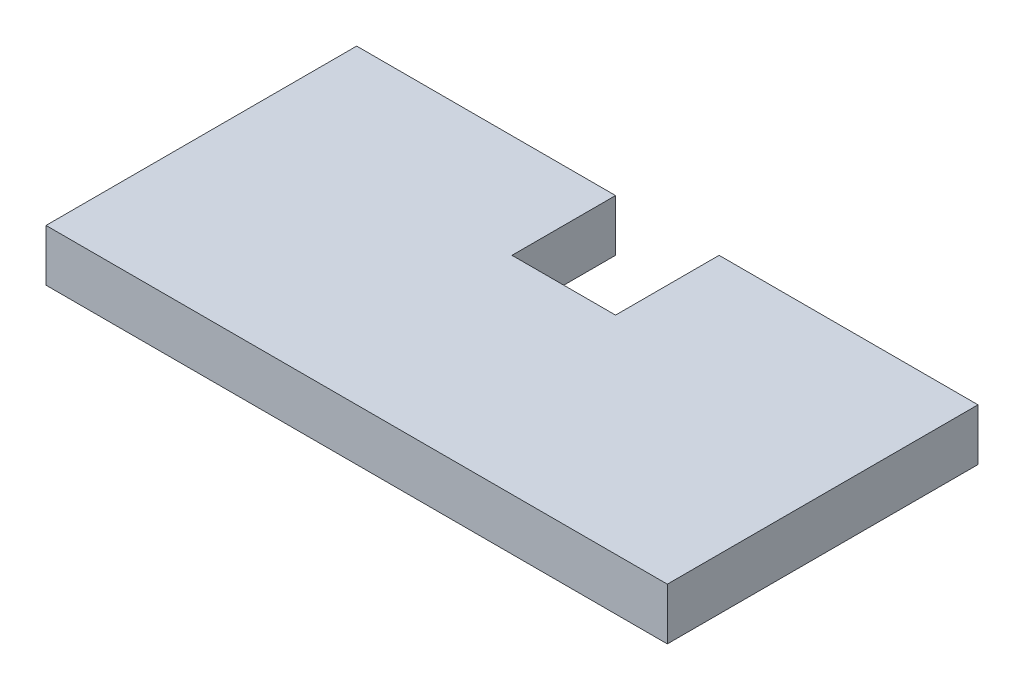
SolidWorks part; units mm, degrees
ref_plane "Front Plane" through (0, 0, 0) normal (0, 0, 1) x (1, 0, 0)
ref_plane "Top Plane" through (0, 0, 0) normal (0, 1, 0) x (1, 0, 0)
ref_plane "Right Plane" through (0, 0, 0) normal (1, 0, 0) x (0, 0, -1)
sketch "Sketch1" plane through (0, 0, 0) normal (0, 1, 0) x (1, 0, 0)
  line L1 (-516.0526, 370.5409) -> (83.9474, 370.5409)
  line L2 (-516.0526, 370.5409) -> (-516.0526, 70.5409)
  line L3 (-516.0526, 70.5409) -> (83.9474, 70.5409)
  line L4 (83.9474, 370.5409) -> (83.9474, 70.5409)
  dimension "D1" = 600
  dimension "D2" = 300
extrude "Boss-Extrude1" add sketch "Sketch1" along normal blind 50 contours L3 L4 L1 L2
sketch "Sketch2" plane through (0, 0, -370.5409) normal (0, 0, -1) x (-1, 0, 0)
  line L0 (516.0526, 50) -> (-83.9474, 50) construction
  line L1 (166.0526, 50) -> (266.0526, 50)
  line L2 (166.0526, 50) -> (166.0526, 0)
  line L3 (166.0526, 0) -> (266.0526, 0)
  line L4 (266.0526, 50) -> (266.0526, 0)
  line L5 (516.0526, 0) -> (-83.9474, 0) construction
  line L6 (-83.9474, 50) -> (-83.9474, 0) construction
  dimension "D1" = 100
  dimension "D2" = 250
  dimension "D3" = 50
extrude "Cut-Extrude1" cut sketch "Sketch2" against normal blind 100 contours L2 L3 L4 L1
equation "\"BaseWidth\" = 600"
equation "\"BaseLength\"= 300"
equation "\"D1@Sketch1\"=\"BaseWidth\""
equation "\"D2@Sketch1\"=\"BaseLength\""
equation "\"BaseHeight\"= 50"
equation "\"D1@Boss-Extrude1\"=\"BaseHeight\""
equation "\"BeamWidth\"= 100"
equation "\"D1@Sketch2\"=\"BeamWidth\""
equation "\"D2@Sketch2\"=(\"BaseWidth\"-\"BeamWidth\")/2"
equation "\"BeamLength\"= 100"
equation "\"D1@Cut-Extrude1\"=\"BeamLength\""
